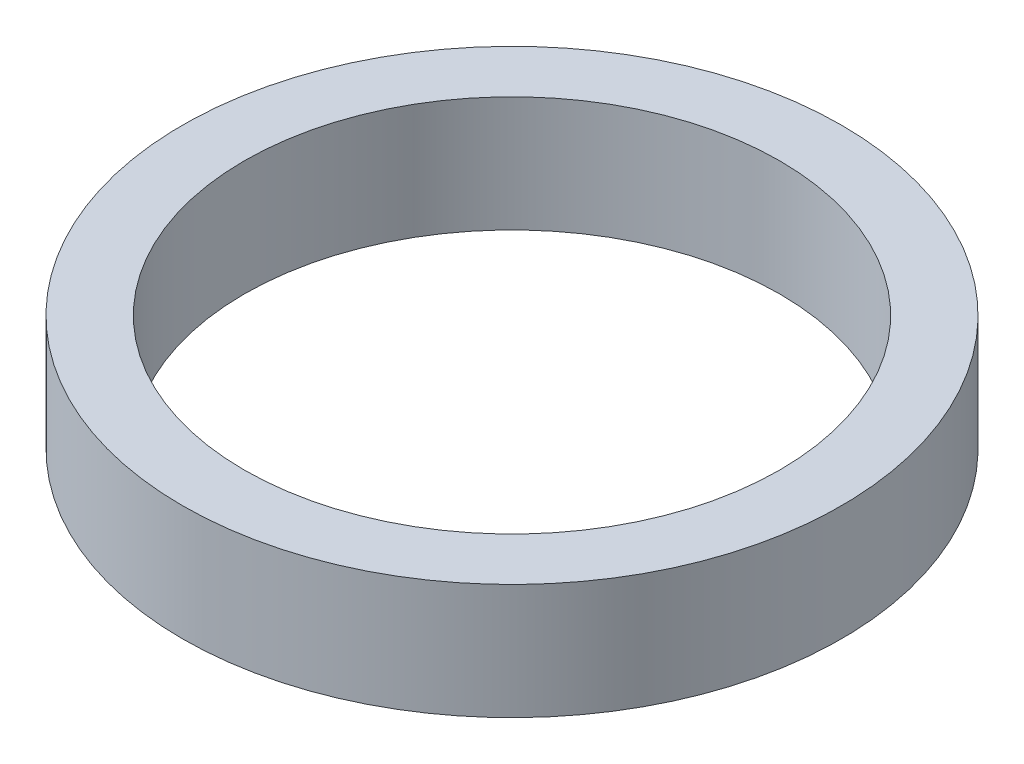
SolidWorks part; units mm, degrees
ref_plane "Front Plane" through (0, 0, 0) normal (0, 0, 1) x (1, 0, 0)
ref_plane "Top Plane" through (0, 0, 0) normal (0, 1, 0) x (1, 0, 0)
ref_plane "Right Plane" through (0, 0, 0) normal (1, 0, 0) x (0, 0, -1)
sketch "Sketch1" plane through (0, 0, 0) normal (0, 1, 0) x (1, 0, 0)
  circle A0 centre (0, 0) radius 40
  dimension "FLANGE_OD" = 80
extrude "Boss-Extrude1" add sketch "Sketch1" along normal blind 14
sketch "Sketch2" plane through (0, 0, 0) normal (0, 1, 0) x (1, 0, 0)
  circle A0 centre (0, 0) radius 32.5
  dimension "BORE_D" = 65
extrude "Cut-Extrude1" cut sketch "Sketch2" along normal through all
sketch "Sketch3" plane through (0, 14, 0) normal (0, 1, 0) x (1, 0, 0)
  circle A0 centre (0, 0) radius 17.74 construction
  circle A1 centre (-17.74, 0) radius 1.5
  dimension "BOLT_D" = 3
  dimension "BOLT_PCD" = 35.48
extrude "Cut-Extrude2" cut sketch "Sketch3" against normal blind 11.9235 rebuild error yes
pattern_circular "CirPattern1" count 5 over 360 rebuild error yes
